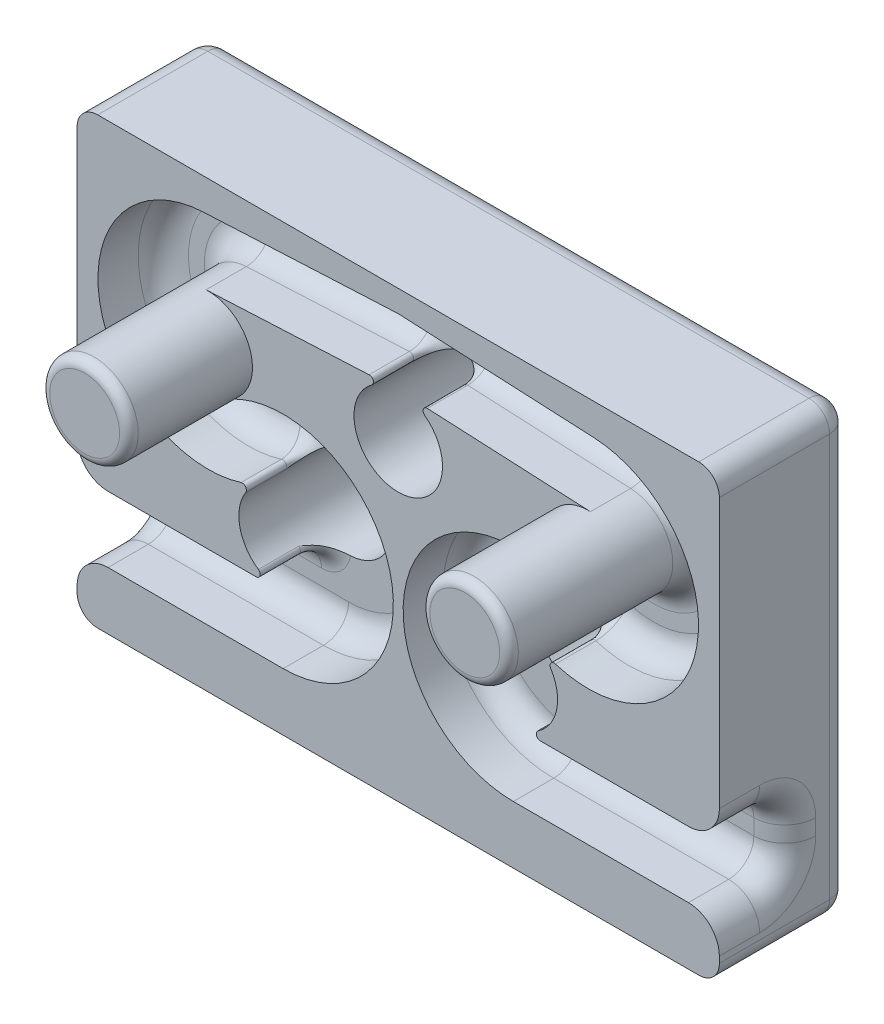
SolidWorks part; units mm, degrees
ref_plane "Front Plane" through (0, 0, 0) normal (0, 0, 1) x (1, 0, 0)
ref_plane "Top Plane" through (0, 0, 0) normal (0, 1, 0) x (1, 0, 0)
ref_plane "Right Plane" through (0, 0, 0) normal (1, 0, 0) x (0, 0, -1)
sketch "Sketch1" plane through (0, 0, 0) normal (0, 0, 1) x (1, 0, 0)
  line L0 (0, 10.795) -> (0, -10.795) construction
  line L1 (-15.5956, 10.795) -> (15.5956, 10.795)
  line L2 (-15.5956, 10.795) -> (-15.5956, -10.795)
  line L3 (-15.5956, -10.795) -> (15.5956, -10.795)
  line L4 (15.5956, 10.795) -> (15.5956, -10.795)
  line L5 (-15.5956, 10.795) -> (15.5956, -10.795) construction
  line L6 (-15.5956, -10.795) -> (15.5956, 10.795) construction
  line L7 (-5.5905, -2.6391) -> (5.5905, -2.6391) construction
  line L8 (-9.2291, 3.9218) -> (9.2291, 3.9218) construction
  circle A0 centre (0, 4.3713) radius 2.1488
  circle A1 centre (5.5905, -2.6391) radius 2.1488
  circle A2 centre (-5.5905, -2.6391) radius 2.1488
  circle A3 centre (-9.2291, 3.9218) radius 2.1488
  circle A4 centre (9.2291, 3.9218) radius 2.1488
  point P0 (0, 0)
  point P14 (0, -2.6391)
  point P18 (0, 3.9218)
  dimension "D6" = 4.2977
  dimension "D1" = 31.1912
  dimension "D2" = 21.59
  dimension "D3" = 8.1559
  dimension "D4" = 11.1811
  dimension "D5" = 6.4237
  dimension "D7" = 18.4582
  dimension "D8" = 6.8732
extrude "Boss-Extrude1" add sketch "Sketch1" along normal blind 6.35
extrude "Boss-Extrude2" add sketch "Sketch1<3>" along normal blind 12.3495 contours A3 | A4 region at (-9.2291, 3.9218, 0) region at (9.2291, 3.9218, 0)
sketch "Sketch1<3>" plane through (0, 0, 0) normal (0, 0, 1) x (1, 0, 0) same geometry as "Sketch1"
sketch "Sketch2" plane through (0, 0, 6.35) normal (0, 0, 1) x (1, 0, 0)
  line L0 (-5.5905, -4.7879) -> (-15.5956, -4.7879)
  line L1 (-15.5956, 10.795) -> (-15.5956, -10.795) construction
  line L2 (-15.5956, -4.7879) -> (-15.5956, -7.9924)
  line L3 (-15.5956, -7.9924) -> (-5.5905, -7.9924)
  line L4 (5.5905, -4.7879) -> (15.5956, -4.7879)
  line L5 (15.5956, -10.795) -> (15.5956, 10.795) construction
  line L6 (15.5956, -4.7879) -> (15.5956, -7.9924)
  line L7 (15.5956, -7.9924) -> (5.5905, -7.9924)
  line L8 (-9.4896, 9.2688) -> (0, 9.7311)
  line L9 (0, 9.7311) -> (9.4896, 9.2688)
  line L10 (-0.1046, 6.5176) -> (0.1046, 6.5176)
  line L11 (-9.3336, 6.0681) -> (-0.1046, 6.5176)
  line L12 (0.1046, 6.5176) -> (9.3336, 6.0681)
  circle A0 centre (-5.5905, -2.6391) radius 2.1488 construction
  circle A1 centre (5.5905, -2.6391) radius 2.1488 construction
  arc A2 (-5.5905, -7.9924) -> (-8.1869, 2.0426) centre (-5.5905, -2.6391) ccw
  arc A3 (5.5905, -7.9924) -> (8.1869, 2.0426) centre (5.5905, -2.6391) cw
  arc A4 (6.6327, -0.7599) -> (9.4896, 9.2688) centre (9.2291, 3.9218) ccw
  arc A5 (-6.6327, -0.7599) -> (-9.4896, 9.2688) centre (-9.2291, 3.9218) cw
  circle A6 centre (-9.2291, 3.9218) radius 2.1488 construction
  circle A7 centre (9.2291, 3.9218) radius 2.1488 construction
  circle A10 centre (0, 4.3713) radius 2.1488 construction
  circle A11 centre (9.2291, 3.9218) radius 2.1488 construction
  circle A12 centre (-9.2291, 3.9218) radius 2.1488 construction
  arc A13 (-6.6327, -0.7599) -> (-5.5905, -4.7879) centre (-5.5905, -2.6391) cw
  arc A14 (5.5905, -4.7879) -> (6.6699, -0.7809) centre (5.5905, -2.6391) cw
  arc A15 (8.1869, 2.0426) -> (9.3336, 6.0681) centre (9.2291, 3.9218) ccw
  arc A16 (-9.3336, 6.0681) -> (-8.1869, 2.0426) centre (-9.2291, 3.9218) ccw
  circle M9 centre (-9.2291, 3.9218) radius 2.1488
  circle M10 centre (5.5905, -2.6391) radius 2.1488
  line M11 (15.5956, -10.795) -> (15.5956, 10.795)
  line M13 (-15.5956, 10.795) -> (-15.5956, -10.795)
  circle M15 centre (0, 4.3713) radius 2.1488
  circle M16 centre (-5.5905, -2.6391) radius 2.1488
  circle M17 centre (9.2291, 3.9218) radius 2.1488
extrude "Cut-Extrude1" cut sketch "Sketch2" against normal blind 3.175 contours A5 L0 L3 A2 L11 L12 A3 L7 L4 A4 L9 L8 M16 M13 M9 M15 M17 M11 M10 region at (-3.8174, -4.4122, 6.35)
fillet "Fillet1" radius 0.2007 6 edges at (5.5905, -4.7879, 4.7625) (6.6327, -0.7599, 4.7625) (-5.5905, -4.7879, 4.7625) (-6.6327, -0.7599, 4.7625) (-0.1046, 6.5176, 4.7625) (0.1046, 6.5176, 4.7625)
fillet "Fillet2" radius 0.4547 2 edges at (-7.0802, 3.9218, 12.3495) (11.3779, 3.9218, 12.3495)
fillet "Fillet3" radius 1.2192 20 edges at (10.5931, -7.9924, 3.175) (1.2177, 6.3212, 3.175) (5.375, 6.2609, 3.175) (11.2957, 3.333, 3.175) (6.7119, -4.6459, 3.175) (-6.7119, -4.6459, 3.175) (-7.4149, -1.258, 3.175) (-4.7448, 9.4999, 3.175) (7.4149, -1.258, 3.175) (4.7448, 9.4999, 3.175) (-10.5931, -7.9924, 3.175) (-1.2177, 6.3212, 3.175) (-5.375, 6.2609, 3.175) (-11.2957, 3.333, 3.175) (0.4078, -1.2981, 3.175) (11.2497, -4.7879, 3.175) (-11.2497, -4.7879, 3.175) (-14.5001, 2.9865, 3.175) (14.5001, 2.9865, 3.175) (-0.4078, -1.2981, 3.175)
fillet "Fillet4" radius 1.5011 10 edges at (-15.5956, -4.7879, 5.3721) (-15.5956, -5.145, 3.5321) (-15.5956, -6.3902, 3.175) (-15.5956, -7.6354, 3.5321) (15.5956, -7.9924, 5.3721) (15.5956, -7.6354, 3.5321) (15.5956, -6.3902, 3.175) (15.5956, -5.145, 3.5321) (-15.5956, -7.9924, 5.3721) (15.5956, -4.7879, 5.3721)
fillet "Fillet5" radius 1.0008 8 edges at (-15.5956, 0, 0) (0, 10.795, 0) (15.5956, 0, 0) (0, -10.795, 0) (15.5956, -10.795, 3.175) (15.5956, 10.795, 3.175) (-15.5956, -10.795, 3.175) (-15.5956, 10.795, 3.175)
